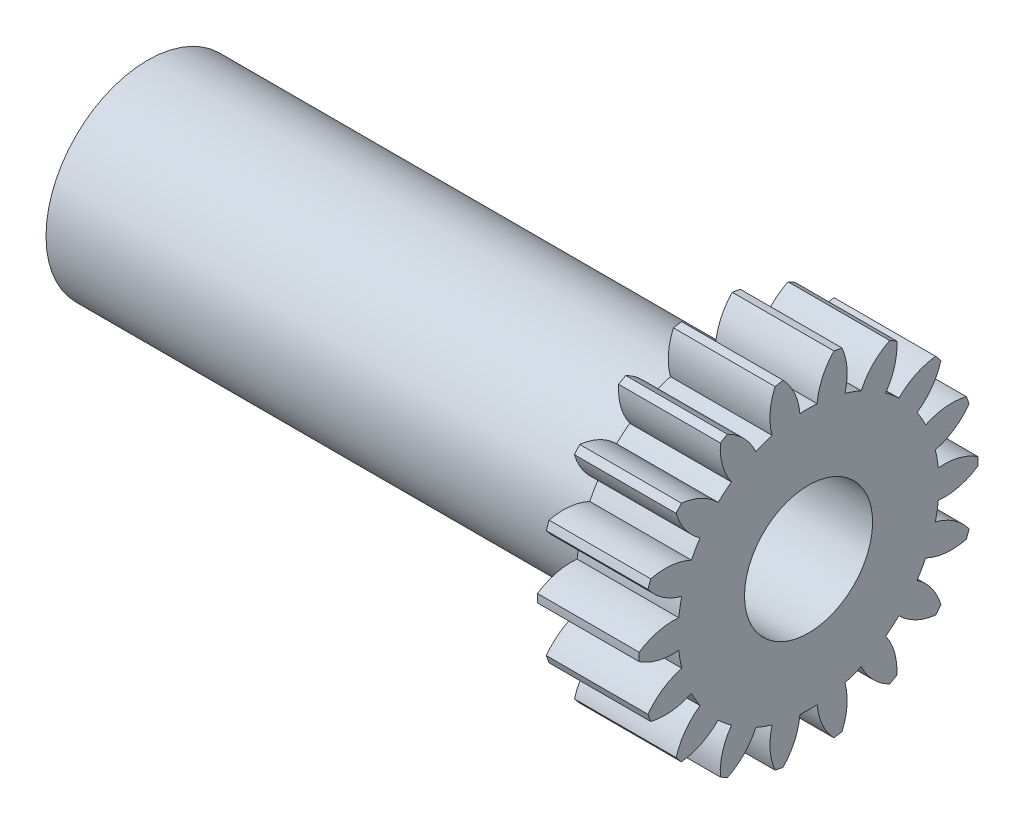
SolidWorks part; units mm, degrees
ref_plane "Plane1" through (0, 0, 0) normal (0, 0, 1) x (1, 0, 0)
ref_plane "Plane2" through (0, 0, 0) normal (0, 1, 0) x (1, 0, 0)
ref_plane "Plane3" through (0, 0, 0) normal (1, 0, 0) x (0, 0, -1)
sketch "HoldingSke" plane through (0, 0, 0) normal (0, 1, 0) x (1, 0, 0)
  line L0 (0, 0) -> (1159.5281, -376.7535)
  line L1 (-15, 0) -> (100, 0) construction
  line L2 (0, 0) -> (-2.1039, 2.3779)
  line L3 (0, 0) -> (-11.863, 4.5341)
  line L4 (0, 0) -> (8.2133, 2.6687)
  line L5 (0, 0) -> (-47.5972, -17.7524)
  line L6 (0, 0) -> (-2.632, -1.7758)
  line L7 (-2.1039, 2.3779) -> (8.8308, 51.9871)
  line L8 (-76.2, 54.61) -> (-75.184, 54.61)
  line L9 (-71.009, 38.7566) -> (-53.1078, 45.2721)
  line L10 (-76.2, 71.12) -> (104.1128, 71.12)
  line L11 (0, 0) -> (-3.175, 0)
  line L12 (-76.2, 101.6) -> (-76.1787, 101.6)
  line L13 (24.9733, 27.94) -> (52.9518, 28.4284)
  line L14 (24.9733, 27.94) -> (25.0241, 27.9398)
  line L15 (24.9733, 27.94) -> (100.4021, 29.52)
  circle A0 centre (0, 0) radius 0.3969
  circle A1 centre (0, 0) radius 4.0767
  circle A2 centre (0, 0) radius 38.1
  circle A3 centre (0, 0) radius 0.3969
  dimension "MHD" = 8.1534
  dimension "Hub_dia" = 76.2
  dimension "Bore" = 0.7937
  dimension "MBD" = 0.7937
  dimension "Num_teeth" = 18
  dimension "Pitch" = 1219.2
  dimension "Overall_len" = 50.8
  dimension "Show_teeth" = 18
  dimension "Thickness" = 3.175
  dimension "OAL" = 50.8001
  dimension "T_dim" = 1.016
  dimension "Ap" = 20
  dimension "H" = 19.05
  dimension "Pitch_radius" = 180.3128
  dimension "Width" = 3.175
  dimension "Backlash" = 0.0213
  dimension "Addendum_fac" = 1
  dimension "Dedendum_fac" = 1.2
  dimension "Clearance_fac" = 0.2
  dimension "Dedendum_add" = 0.0508
sketch "BasProSke" plane through (0, 0, 0) normal (0, 1, 0) x (1, 0, 0)
  line L0 (-10, 0) -> (60, 0) construction
  line L1 (0, 0) -> (0, 5.2917)
  line L2 (0, 0) -> (3.175, 0)
  line L3 (3.175, 0) -> (3.175, 5.2917)
  line L4 (3.175, 5.2917) -> (0, 5.2917)
  dimension "Thickness" = 3.175
  dimension "Diameter" = 10.5833
revolve "Base-Revolve" add sketch "BasProSke" angle 360 about L0
sketch "TooCutSke" plane through (0, 0, 0) normal (1, 0, 0) x (0, 0, -1)
  line L1 (0, 0) -> (0, 107) construction
  line L2 (0, 0) -> (-0.4524, 4.741) construction
  line L3 (0, 0) -> (-1.6488, 9.3507) construction
  line L4 (-0.4524, 4.741) -> (-0.8244, 4.6754) construction
  arc A0 (0.27, 4.0677) -> (-0.27, 4.0677) centre (0, 0) ccw
  arc A1 (0.8145, 5.2543) -> (-0.8145, 5.2543) centre (0, 0) ccw
  circle A2 centre (0, 0) radius 4.7625 construction
  circle A3 centre (0, 0) radius 4.4753 construction
  arc A4 (-0.27, 4.0677) -> (-0.8145, 5.2543) centre (-2.1688, 3.9146) ccw
  arc A5 (0.8145, 5.2543) -> (0.27, 4.0677) centre (2.1688, 3.9146) ccw
  dimension "Root_dia" = 8.1534
  dimension "Overcut_dia" = 10.6341
  dimension "Pitch_dia" = 9.525
  dimension "Base_dia" = 8.9506
  dimension "Flank_rad" = 1.905
  dimension "Half_ang" = 10
  dimension "Half_CT" = 0.3777
extrude "ToothCut" cut sketch "TooCutSke" along normal through all
fillet "Breaks" [suppressed] radius 0.0106 tangent propagation no
fillet "RootFillets" [suppressed] radius 0.1566
pattern_circular "TeethCuts" count 18 every 20 about axis through (-10, 0, 0) along (1, 0, 0) of "ToothCut", "RootFillets", "Breaks"
sketch "HubNeaOneSke" plane through (0, 0, 0) normal (-1, 0, 0) x (0, 0, 1)
  circle A0 centre (0, 0) radius 4.0767
  dimension "Diameter" = 8.1534
extrude "HubNearOne" [suppressed] add sketch "HubNeaOneSke" along normal blind 47.6251
sketch "HubNeaBotSke" plane through (0, 0, 0) normal (-1, 0, 0) x (0, 0, 1)
  circle A0 centre (0, 0) radius 4.0767
  dimension "Diameter" = 8.1534
extrude "HubNearBoth" [suppressed] add sketch "HubNeaBotSke" along normal blind 23.8125
ref_plane "FarPln" through (3.175, 0, 0) normal (1, 0, 0) x (0, 0, -1)
sketch "HubFarSke" plane through (3.175, 0, 0) normal (1, 0, 0) x (0, 0, -1)
  circle A0 centre (0, 0) radius 4.0767
  dimension "Diameter" = 8.1534
extrude "HubFar" [suppressed] add sketch "HubFarSke" along normal blind 23.8125
sketch "BorSke" plane through (0, 0, 0) normal (1, 0, 0) x (0, 0, -1)
  circle A0 centre (0, 0) radius 0.3969
  dimension "Diameter" = 0.7937
extrude "Bore" [suppressed] cut sketch "BorSke" along normal mid plane 101.6001
sketch "KeySke" plane through (0, 0, 0) normal (1, 0, 0) x (0, 0, -1)
  line L0 (-0.127, 0) -> (-0.127, 0.6191)
  line L1 (-0.127, 0.6191) -> (0.127, 0.6191)
  line L2 (0.127, 0.6191) -> (0.127, 0)
  line L3 (0, 0) -> (0, 34) construction
  line L4 (-0.127, 0) -> (0.127, 0)
  dimension "Offset" = 0.6191
  dimension "Width" = 0.254
extrude "Keyway" [suppressed] cut sketch "KeySke" along normal mid plane 101.6001
pattern_circular "Keyway2" [suppressed] count 2 every 90 about axis through (-10, 0, 0) along (1, 0, 0) reverse direction yes
sketch "Sketch1" [suppressed] plane through (0, 0, 0) normal (-1, 0, 0) x (0, 0, 1)
  circle A0 centre (0, 0) radius 2.7781
  dimension "D1" = 5.5562
extrude "Cut-Extrude2" [suppressed] cut sketch "Sketch1" against normal offset from surface (1.5875 mm away) 1.5875 up to face at (3.175, 0, 0)
sketch "Sketch2" plane through (0, 0, 0) normal (-1, 0, 0) x (0, 0, 1)
  circle A0 centre (0, 0) radius 2
  circle A1 centre (0, 0) radius 3.175
  dimension "D1" = 4
  dimension "D2" = 6.35
extrude "Cut-Extrude3" cut sketch "Sketch2" against normal through all contours A0 region at (0, 0, 0)
extrude "Boss-Extrude1" add sketch "Sketch2<3>" along normal blind 17.4625
sketch "Sketch2<3>" plane through (0, 0, 0) normal (-1, 0, 0) x (0, 0, 1) same geometry as "Sketch2"
ref_plane "Plane4" through (1.5875, 0, 0) normal (-1, 0, 0) x (0, 0, 1)
sketch "Sketch3" plane through (1.5875, 0, 0) normal (-1, 0, 0) x (0, 0, 1)
  circle A0 centre (0, 0) radius 4.7625
  dimension "D1" = 9.525
equation "' \"Pitch@HoldingSke\" = 4"
equation "' \"Num_teeth@HoldingSke\" = 12"
equation "' \"Ap@HoldingSke\" =  20"
equation "' \"Ap@HoldingSke\" = 20"
equation "' \"Width@HoldingSke\" = 0.5"
equation "' \"Hub_dia@HoldingSke\"= 1"
equation "' \"Hub_dia@HoldingSke\" = 1"
equation "' \"Overall_len@HoldingSke\" = 1.0"
equation "' \"Bore@HoldingSke\" = 0.75"
equation "' \"T_dim@HoldingSke\" = 0.85"
equation "' \"Width@KeySke\" = 0.25"
equation "' \"Show_teeth@HoldingSke\" = 13"
equation "' \"Backlash@HoldingSke\" = 0.009"
equation "' \"Addendum_fac@HoldingSke\" = 1.0"
equation "' \"Dedendum_fac@HoldingSke\" = 1.25"
equation "' \"Dedendum_add@HoldingSke\" = 0.00005"
equation "' \"Clearance_fac@HoldingSke\" = 0.25"
equation "' \"Pitch@HoldingSke\" = 0.5"
equation "' \"Num_teeth@HoldingSke\" = 23"
equation "' \"Show_teeth@HoldingSke\" = 23"
equation "' \"Backlash@HoldingSke\" = 0.0375"
equation "\"Overcut_dia@TooCutSke\" = (\"Num_teeth@HoldingSke\" + 2 * \"Addendum_fac@HoldingSke\") / \"Pitch@HoldingSke\" + 0.002"
equation "\"Pitch_dia@TooCutSke\" = \"Num_teeth@HoldingSke\" / \"Pitch@HoldingSke\""
equation "\"Base_dia@TooCutSke\" = \"Num_teeth@HoldingSke\" / \"Pitch@HoldingSke\" * cos((\"Ap@HoldingSke\"  * 3.14159265 / 180))"
equation "\"Root_dia@TooCutSke\" = (\"Num_teeth@HoldingSke\" + 2) / \"Pitch@HoldingSke\" - 2 * (\"Addendum_fac@HoldingSke\" + \"Dedendum_fac@HoldingSke\") / \"Pitch@HoldingSke\" - \"Dedendum_add@HoldingSke\" * 2"
equation "\"Half_ang@TooCutSke\" = 180 / \"Num_teeth@HoldingSke\""
equation "\"Half_CT@TooCutSke\" = \"Num_teeth@HoldingSke\" / \"Pitch@HoldingSke\" * sin((3.14159265 / 2 / \"Num_teeth@HoldingSke\")) / 2 - 7 * \"Backlash@HoldingSke\" / 4"
equation "\"Flank_rad@TooCutSke\" = \"Num_teeth@HoldingSke\" / \"Pitch@HoldingSke\" / 5"
equation "\"Radius@RootFillets\" = \"Clearance_fac@HoldingSke\" / \"Pitch@HoldingSke\" + \"Dedendum_add@HoldingSke\""
equation "\"Break_rad@Breaks\" = 0.02 / \"Pitch@HoldingSke\""
equation "\"Thickness@HoldingSke\" = \"Width@HoldingSke\""
equation "\"OAL@HoldingSke\" = \"Thickness@HoldingSke\""
equation "\"MHD@HoldingSke\" = (\"Num_teeth@HoldingSke\" + 2) / \"Pitch@HoldingSke\" - 2 * (\"Addendum_fac@HoldingSke\" + \"Dedendum_fac@HoldingSke\")  / \"Pitch@HoldingSke\" - \"Dedendum_add@HoldingSke\" * 2"
equation "\"MBD@HoldingSke\" = (\"Num_teeth@HoldingSke\" + 2) / \"Pitch@HoldingSke\" - 2 * (\"Addendum_fac@HoldingSke\" + \"Dedendum_fac@HoldingSke\")  / \"Pitch@HoldingSke\" - \"Dedendum_add@HoldingSke\" * 2 - 0.002"
equation "\"MHD@HoldingSke\" = ((sgn( \"MHD@HoldingSke\" - \"Hub_dia@HoldingSke\" )-1)*( \"MHD@HoldingSke\" - \"Hub_dia@HoldingSke\" ))/-2+ \"Hub_dia@HoldingSke\""
equation "\"MBD@HoldingSke\" = ((sgn( \"MBD@HoldingSke\" - \"Bore@HoldingSke\" )-1)*( \"MBD@HoldingSke\" - \"Bore@HoldingSke\" ))/-2+ \"Bore@HoldingSke\""
equation "\"OAL@HoldingSke\" = ((sgn( \"OAL@HoldingSke\" - \"Overall_len@HoldingSke\" )+1)*( \"OAL@HoldingSke\" - \"Overall_len@HoldingSke\" ))/2 + \"Overall_len@HoldingSke\" + 0.000002"
equation "\"Num_teeth@TeethCuts\" = int( \"Show_teeth@HoldingSke\" ) + 1"
equation "\"Num_teeth@TeethCuts\" = ((sgn( \"Num_teeth@TeethCuts\" - \"Num_teeth@HoldingSke\" )-1)*( \"Num_teeth@TeethCuts\" - \"Num_teeth@HoldingSke\" ))/-2+ \"Num_teeth@HoldingSke\""
equation "\"Num_teeth@TeethCuts\" = ((sgn( \"Num_teeth@TeethCuts\" - 2.0)+1)*( \"Num_teeth@TeethCuts\" - 2.0))/2 +2.0"
equation "\"Angle@TeethCuts\" = 360.0 / \"Num_teeth@HoldingSke\""
equation "\"Diameter@BasProSke\" = (\"Num_teeth@HoldingSke\" + 2 * \"Addendum_fac@HoldingSke\") / \"Pitch@HoldingSke\""
equation "\"Thickness@BasProSke\"  = \"Thickness@HoldingSke\""
equation "' \"Fillet_rad@BasProSke\" =  \"Thickness@HoldingSke\" * 0.05"
equation "' \"Fillet_rad@BasProSke\" = \"Thickness@HoldingSke\" * 0.05"
equation "\"MHD@HoldingSke\" = ((sgn( \"MHD@HoldingSke\" - \"Root_dia@TooCutSke\" )-1)*( \"MHD@HoldingSke\" - \"Root_dia@TooCutSke\" ))/-2+ \"Root_dia@TooCutSke\""
equation "\"Diameter@HubNeaOneSke\" = \"MHD@HoldingSke\""
equation "\"Length@HubNearOne\" = \"OAL@HoldingSke\" - \"Thickness@BasProSke\""
equation "\"Diameter@HubNeaBotSke\" = \"MHD@HoldingSke\""
equation "\"Length@HubNearBoth\" = ( \"OAL@HoldingSke\" - \"Thickness@BasProSke\" ) / 2.0"
equation "\"Thickness@FarPln\" = \"Thickness@BasProSke\""
equation "\"Diameter@HubFarSke\" = \"MHD@HoldingSke\""
equation "\"Length@HubFar\" = ( \"OAL@HoldingSke\" - \"Thickness@BasProSke\" ) / 2.0"
equation "\"Diameter@BorSke\" = \"MBD@HoldingSke\""
equation "\"D1@Bore\" = \"OAL@HoldingSke\" * 2.0"
equation "\"D1@Keyway\" = \"OAL@HoldingSke\" * 2.0"
equation "\"Offset@KeySke\" = \"T_dim@HoldingSke\" - \"MBD@HoldingSke\" / 2.0"
